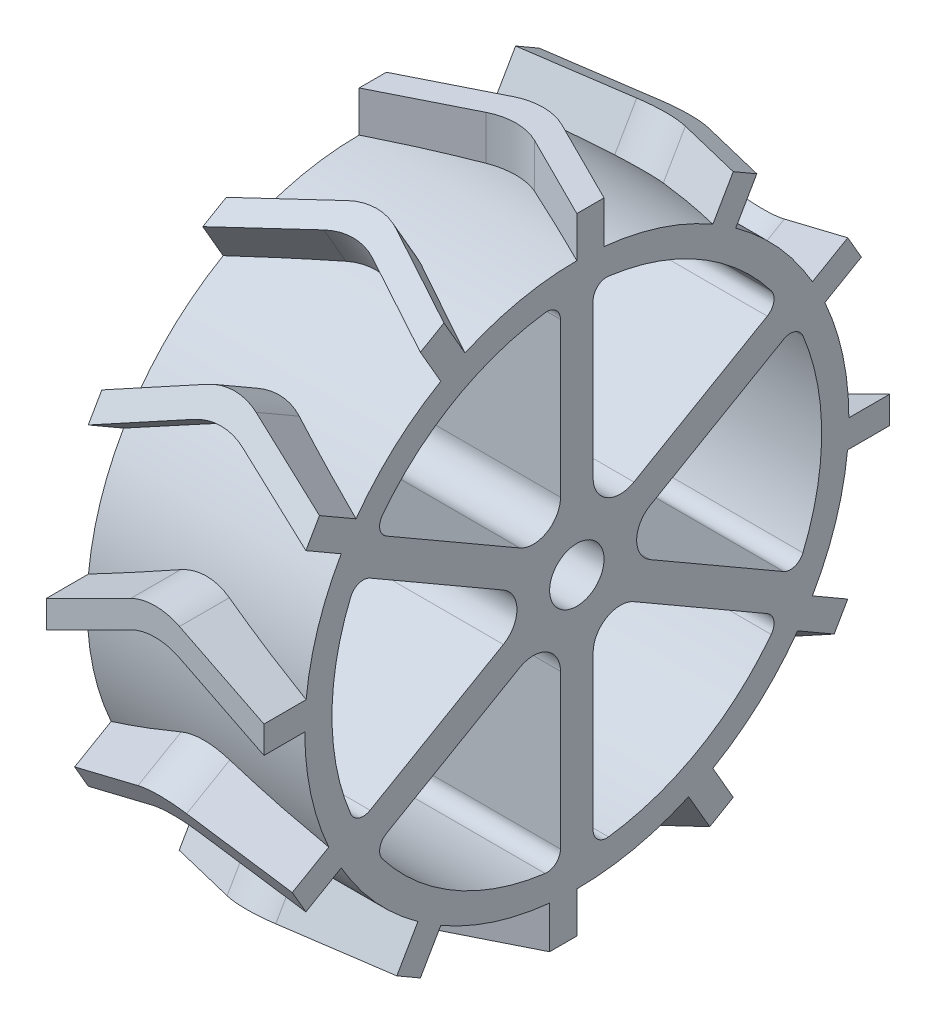
SolidWorks part; units mm, degrees
ref_plane "Front Plane" through (0, 0, 0) normal (0, 0, 1) x (1, 0, 0)
ref_plane "Top Plane" through (0, 0, 0) normal (0, 1, 0) x (1, 0, 0)
ref_plane "Right Plane" through (0, 0, 0) normal (1, 0, 0) x (0, 0, -1)
sketch "Sketch2" plane through (0, 0, 0) normal (1, 0, 0) x (0, 0, -1)
  circle A2 centre (0, 0) radius 50
  dimension "D1" = 100
extrude "Boss-Extrude1" add sketch "Sketch2" along normal blind 40
sketch "Sketch4" plane through (0, 0, 0) normal (0, 1, 0) x (1, 0, 0)
  line L8 (0, 0) -> (40, 0) construction
  line L9 (40, -50) -> (40, 50) construction
  line L10 (0, 0) -> (15.5279, 7.7639)
  line L11 (24.4721, 7.7639) -> (40, 0)
  line L12 (40, 0) -> (40, 5)
  line L13 (40, 5) -> (24.4721, 12.7639)
  line L14 (15.5279, 12.7639) -> (0, 5)
  line L15 (0, 50) -> (0, -50) construction
  line L16 (0, 5) -> (0, 0)
  arc A0 (24.4721, 12.7639) -> (15.5279, 12.7639) centre (20, 3.8197) ccw
  arc A1 (15.5279, 7.7639) -> (24.4721, 7.7639) centre (20, -1.1803) cw
  point P4 (20, 0)
  point P18 (20, 15)
  point P21 (20, 10)
  dimension "D3" = 10
  dimension "D1" = 5
  dimension "D2" = 5
  dimension "D4" = 10
extrude "Boss-Extrude2" add sketch "Sketch4" along normal blind 57.5
pattern_circular "CirPattern2" count 12 over 360 about axis through (40, 0, 0) along (-1, 0, 0) of "Boss-Extrude2"
sketch "Sketch5" plane through (0, 0, 0) normal (-1, 0, 0) x (0, 0, 1)
  line L0 (0, 0) -> (0, 50) construction
  line L1 (0, 0) -> (43.3013, 25) construction
  line L6 (3, 42.1426) -> (3, 5.1962)
  line L8 (34.9966, 23.6694) -> (3, 5.1962)
  arc A0 (49.7494, 5) -> (43.3013, 25) centre (0, 0) ccw construction
  arc A2 (5.8235, 44.6216) -> (35.7317, 27.3541) centre (0, 0) cw
  arc A6 (35.7317, 27.3541) -> (34.9966, 23.6694) centre (33.7466, 25.8344) cw
  arc A7 (5.8235, 44.6216) -> (3, 42.1426) centre (5.5, 42.1426) ccw
  arc A10 (40.5842, 29.2048) -> (25, 43.3013) centre (0, 0) ccw construction
  point P7 (0, 0)
  point P8 (3, 5.1962)
  point P9 (0, 0)
  point P10 (-32.9917, 43.6525)
  point P11 (0, 44.8999)
  point P12 (0, 0)
  point P13 (3, 5.1966)
  point P22 (3, 44.8999)
  point P23 (3.0165, 5.1966)
  point P25 (0, 0)
  point P27 (0, 0)
  point P28 (0, 0)
  point P29 (3, 25.8586)
  point P30 (0, 0)
  point P31 (0, 0)
  point P32 (-22.2013, 31.2052)
  point P33 (0, 0)
  point P36 (0, 0)
  point P37 (3, 5.1962)
  point P38 (0, 0)
  dimension "D1" = 3
  dimension "D2" = 5
  dimension "D8" = 2.5
  dimension "D7" = 3
  dimension "D9" = 60
extrude "Cut-Extrude3" cut sketch "Sketch5" against normal up to next
sketch "Sketch6" plane through (0, 0, 0) normal (-1, 0, 0) x (0, 0, 1)
  circle A0 centre (0, 0) radius 5
  dimension "D1" = 10
extrude "Cut-Extrude4" cut sketch "Sketch6" against normal up to next
fillet "Fillet1" radius 5 1 edges at (20, 5.1962, 3)
pattern_circular "CirPattern3" count 6 over 360 about axis through (0, 0, 0) along (1, 0, 0) of "Cut-Extrude3", "Fillet1"
